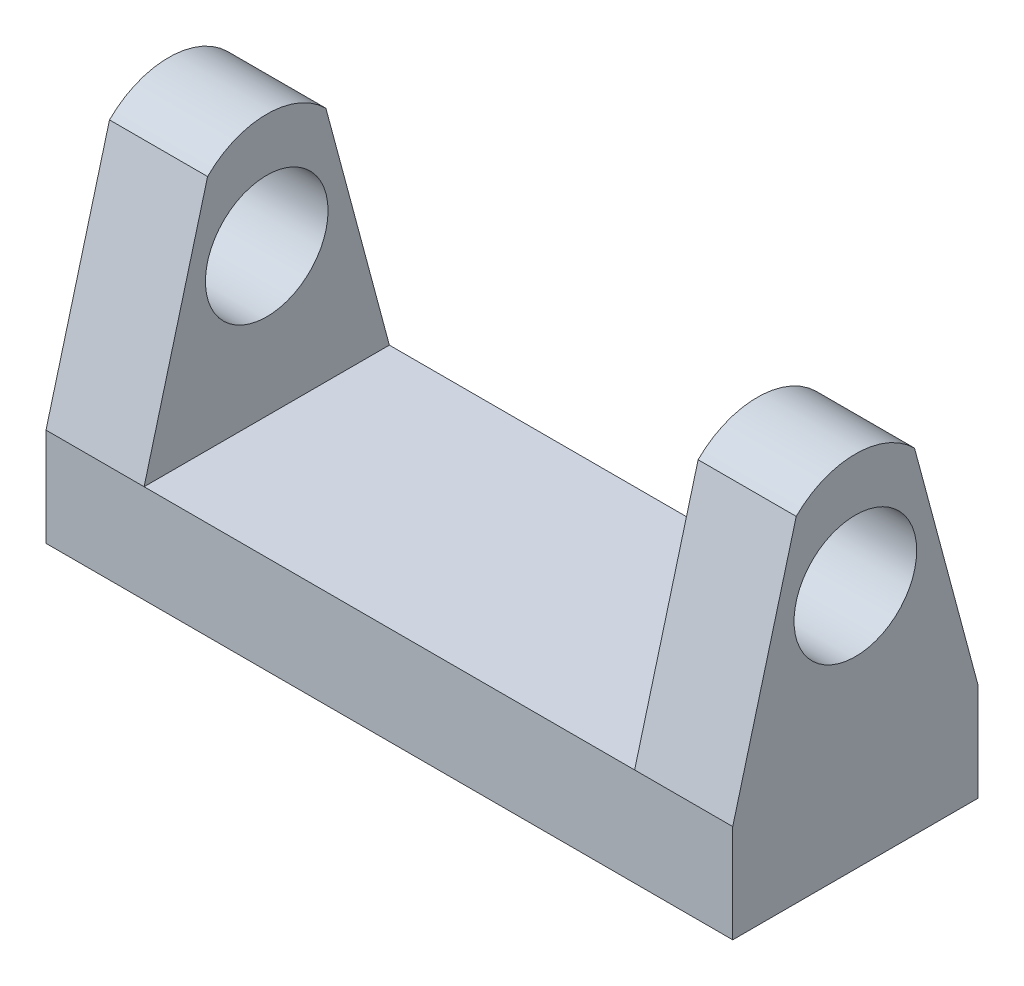
SolidWorks part; units mm, degrees
material "ABS"
ref_plane "Front Plane" through (0, 0, 0) normal (0, 0, 1) x (1, 0, 0)
ref_plane "Top Plane" through (0, 0, 0) normal (0, 1, 0) x (1, 0, 0)
ref_plane "Right Plane" through (0, 0, 0) normal (1, 0, 0) x (0, 0, -1)
sketch "Sketch1" plane through (0, 0, 0) normal (0, 1, 0) x (1, 0, 0)
  line L1 (-17.78, -6.35) -> (17.78, -6.35)
  line L2 (-17.78, -6.35) -> (-17.78, 6.35)
  line L3 (-17.78, 6.35) -> (17.78, 6.35)
  line L4 (17.78, -6.35) -> (17.78, 6.35)
  line L5 (-17.78, -6.35) -> (17.78, 6.35) construction
  line L6 (-17.78, 6.35) -> (17.78, -6.35) construction
  point P0 (0, 0)
  dimension "D1" = 35.56
extrude "Boss-Extrude1" add sketch "Sketch1" along normal blind 5.08 contours L3 L4 L1 L2
sketch "Sketch2" plane through (17.78, 0, 0) normal (1, 0, 0) x (0, 0, -1)
  line L0 (-6.35, 5.08) -> (-3.063, 17.3473)
  line L1 (6.35, 5.08) -> (3.063, 17.3473)
  line L2 (-6.35, 5.08) -> (6.35, 5.08) construction
  line L3 (-6.35, 5.08) -> (6.35, 5.08)
  arc A0 (-3.063, 17.3473) -> (3.063, 17.3473) centre (0, 14.2843) cw
  dimension "D1" = 75
  dimension "D2" = 75
extrude "Boss-Extrude2" add sketch "Sketch2" against normal blind 5.08
ref_plane "Plane1" through (0, 0, 0) normal (1, 0, 0) x (0, 0, -1)
mirror "Mirror1" about plane through (0, 0, 0) normal (1, 0, 0) of "Boss-Extrude2"
sketch "Sketch3" plane through (17.78, 0, 0) normal (1, 0, 0) x (0, 0, -1)
  line L0 (-6.35, 0) -> (6.35, 0) construction
  circle A0 centre (0, 12.7) radius 3.175
  dimension "D1" = 12.7
extrude "Cut-Extrude1" cut sketch "Sketch3" against normal through all
